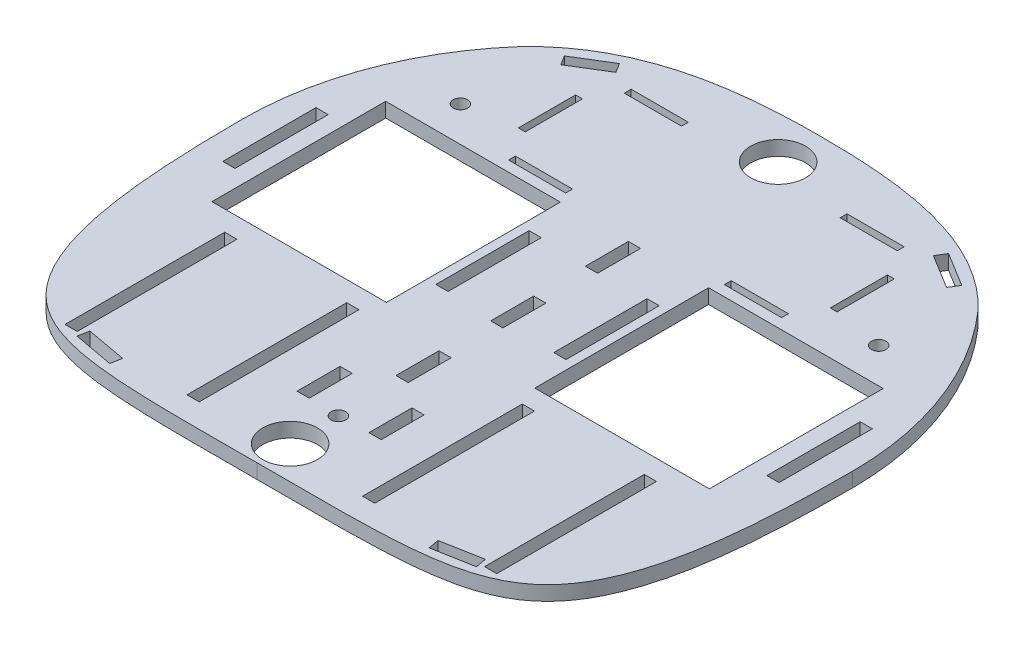
SolidWorks part; units mm, degrees
ref_plane "Front Plane" through (0, 0, 0) normal (0, 0, 1) x (1, 0, 0)
ref_plane "Top Plane" through (0, 0, 0) normal (0, 1, 0) x (1, 0, 0)
ref_plane "Right Plane" through (0, 0, 0) normal (1, 0, 0) x (0, 0, -1)
sketch "Sketch1" plane through (0, 0, 0) normal (0, 1, 0) x (1, 0, 0)
  line L0 (0, 0) -> (-157.9039, -157.9039) construction
  line L1 (0, -127) -> (0, 133.35) construction
  arc A0 (133.35, 0) -> (-133.35, 0) centre (0, 0) ccw
  spline S0 degree 3 poles (-133.35, 0) (-133.35, -51.198) (-123.8034, -129.8051) (-58.428, -127) (0, -127) knots 0 0 0 0 0.502616 1 1 1 1
  spline S1 degree 3 poles (133.35, 0) (133.35, -51.198) (123.8034, -129.8051) (58.428, -127) (0, -127) knots 0 0 0 0 0.502616 1 1 1 1
  dimension "D1" = 266.7
extrude "Base" add sketch "Sketch1" along normal blind 6.35
sketch "ShaftLayout" plane through (0, 6.35, 0) normal (0, 1, 0) x (1, 0, 0)
  line L0 (-133.35, 0) -> (133.35, 0) construction
  line L1 (0, 133.35) -> (0, -127) construction
  line L2 (-114.7053, -6.35) -> (-104.7993, -6.35)
  line L3 (-36.3853, -38) -> (-94.3853, -38)
  line L4 (-36.3853, -38) -> (-36.3853, 38)
  line L5 (-36.3853, 38) -> (-94.3853, 38)
  line L6 (-94.3853, -38) -> (-94.3853, 38)
  line L7 (-36.3853, -38) -> (-94.3853, 38) construction
  line L8 (-36.3853, 38) -> (-94.3853, -38) construction
  line L9 (-102.0053, -15.875) -> (-104.7993, -15.875)
  line L10 (-102.0053, -15.875) -> (-102.0053, 15.875)
  line L11 (-102.0053, 15.875) -> (-104.7993, 15.875)
  line L12 (-104.7993, -15.875) -> (-104.7993, 15.875)
  line L13 (-102.0053, -15.875) -> (-104.7993, 15.875) construction
  line L14 (-102.0053, 15.875) -> (-104.7993, -15.875) construction
  line L15 (-114.7053, -6.35) -> (-114.7053, 6.35)
  line L16 (-104.7993, -6.35) -> (-104.7993, 6.35)
  line L17 (-114.7053, 6.35) -> (-104.7993, 6.35)
  line L18 (-114.7053, -6.35) -> (-104.7993, 6.35) construction
  line L19 (-104.7993, -6.35) -> (-114.7053, 6.35) construction
  line L20 (-116.2928, -9.525) -> (-114.7053, -9.525)
  line L21 (-116.2928, -9.525) -> (-116.2928, 9.525)
  line L22 (-114.7053, -9.525) -> (-114.7053, 9.525)
  line L23 (-116.2928, 9.525) -> (-114.7053, 9.525)
  line L24 (-116.2928, -9.525) -> (-114.7053, 9.525) construction
  line L25 (-114.7053, -9.525) -> (-116.2928, 9.525) construction
  line L26 (-127.4053, -7.9375) -> (-116.2928, -7.9375)
  line L27 (-127.4053, -7.9375) -> (-127.4053, 7.9375)
  line L28 (-116.2928, -7.9375) -> (-116.2928, 7.9375)
  line L29 (-127.4053, 7.9375) -> (-116.2928, 7.9375)
  line L30 (-127.4053, -7.9375) -> (-116.2928, 7.9375) construction
  line L31 (-116.2928, -7.9375) -> (-127.4053, 7.9375) construction
  line L32 (-17.3353, -7.9375) -> (-28.4478, -7.9375)
  line L33 (-30.0353, -9.525) -> (-28.4478, -9.525)
  line L34 (-30.0353, -9.525) -> (-30.0353, 9.525)
  line L35 (-30.0353, 9.525) -> (-28.4478, 9.525)
  line L36 (-28.4478, -9.525) -> (-28.4478, 9.525)
  line L37 (-30.0353, -9.525) -> (-28.4478, 9.525) construction
  line L38 (-30.0353, 9.525) -> (-28.4478, -9.525) construction
  line L39 (-17.3353, -7.9375) -> (-17.3353, 7.9375)
  line L40 (-28.4478, -7.9375) -> (-28.4478, 7.9375)
  line L41 (-17.3353, 7.9375) -> (-28.4478, 7.9375)
  line L42 (-17.3353, -7.9375) -> (-28.4478, 7.9375) construction
  line L43 (-28.4478, -7.9375) -> (-17.3353, 7.9375) construction
  line L45 (-67.3853, -10.033) -> (-56.3853, -10.033)
  line L46 (-67.3853, -10.033) -> (-67.3853, 10.033)
  line L47 (-67.3853, 10.033) -> (-56.3853, 10.033)
  line L48 (-56.3853, -10.033) -> (-56.3853, 10.033)
  line L49 (-67.3853, -10.033) -> (-56.3853, 10.033) construction
  line L50 (-67.3853, 10.033) -> (-56.3853, -10.033) construction
  arc A0 (133.35, 0) -> (-133.35, 0) centre (0, 0) ccw construction
  point P10 (-65.3853, 0)
  point P15 (-103.4023, 0)
  point P20 (-29.2416, 0)
  point P21 (-109.7523, 0)
  point P22 (-115.4991, 0)
  point P23 (-121.8491, 0)
  point P40 (-61.8853, 0)
  point P41 (-22.8916, 0)
  dimension "D1" = 58
  dimension "D2" = 76
  dimension "D3" = 7.62
  dimension "D4" = 2.794
  dimension "D5" = 31.75
  dimension "D6" = 9.906
  dimension "D7" = 12.7
  dimension "D8" = 19.05
  dimension "D9" = 1.5875
  dimension "D10" = 12.7
  dimension "D11" = 15.875
  dimension "D12" = 19.05
  dimension "D13" = 1.5875
  dimension "D14" = 15.875
  dimension "D15" = 12.7
  dimension "D16" = 6.35
  dimension "D17" = 20.066
  dimension "D18" = 20
  dimension "D19" = 11
sketch "MotorLayout" plane through (0, 6.35, 0) normal (0, 1, 0) x (1, 0, 0)
  line L0 (-94.3853, -81.74) -> (-114.3853, -81.74) construction
  line L1 (-94.3853, -110.24) -> (-18.3853, -110.24)
  line L2 (-94.3853, -110.24) -> (-94.3853, -53.24)
  line L3 (-94.3853, -53.24) -> (-18.3853, -53.24)
  line L4 (-18.3853, -110.24) -> (-18.3853, -53.24)
  line L5 (-94.3853, -110.24) -> (-18.3853, -53.24) construction
  line L6 (-94.3853, -53.24) -> (-18.3853, -110.24) construction
  line L7 (-114.7053, -92.0587) -> (-104.7993, -92.0587)
  line L8 (-104.7993, -97.615) -> (-102.0053, -97.615)
  line L9 (-104.7993, -97.615) -> (-104.7993, -65.865)
  line L10 (-104.7993, -65.865) -> (-102.0053, -65.865)
  line L11 (-102.0053, -97.615) -> (-102.0053, -65.865)
  line L12 (-104.7993, -97.615) -> (-102.0053, -65.865) construction
  line L13 (-104.7993, -65.865) -> (-102.0053, -97.615) construction
  line L14 (-36.3853, -38) -> (-94.3853, -38) construction
  line L15 (-114.7053, -92.0587) -> (-114.7053, -71.4212)
  line L16 (-104.7993, -92.0587) -> (-104.7993, -71.4212)
  line L17 (-114.7053, -71.4212) -> (-104.7993, -71.4212)
  line L18 (-114.7053, -92.0587) -> (-104.7993, -71.4212) construction
  line L19 (-104.7993, -92.0587) -> (-114.7053, -71.4212) construction
  line L20 (-103.4023, -1000) -> (-103.4023, 49000) construction
  line L21 (-34.8953, -53.24) -> (-34.8953, -110.24) construction
  point P0 (-56.3853, -81.74)
  point P7 (-103.4023, -81.74)
  point P14 (-109.7523, -81.74)
  dimension "D1" = 20
  dimension "D2" = 76
  dimension "D3" = 57
  dimension "D4" = 2.794
  dimension "D5" = 15.24
  dimension "D6" = 31.75
  dimension "D7" = 20.6375
  dimension "D8" = 12.7
  dimension "D9" = 7.62
  dimension "D10" = 16.51
sketch "Sketch6" plane through (0, 6.35, 0) normal (0, 1, 0) x (1, 0, 0)
  line L0 (-36.3853, -38) -> (-36.3853, 38) construction
  line L1 (-32.4166, -38) -> (-108.7681, -38)
  line L2 (-32.4166, -38) -> (-32.4166, 38)
  line L3 (-32.4166, 38) -> (-108.7681, 38)
  line L4 (-108.7681, -38) -> (-108.7681, 38)
  line L5 (-28.4478, -9.525) -> (-28.4478, 9.525) construction
  line L6 (-104.7993, -15.875) -> (-104.7993, 15.875) construction
  line L7 (0, 133.35) -> (0, -127) construction
  line L8 (28.4478, 20.3835) -> (23.1138, -20.3835) construction
  line L9 (28.4478, -20.3835) -> (23.1138, 20.3835) construction
  line L10 (116.2928, 20.3835) -> (121.6268, -20.3835) construction
  line L11 (116.2928, -20.3835) -> (121.6268, 20.3835) construction
  line L12 (-133.35, 0) -> (133.35, 0) construction
  line L13 (-116.2928, -20.3835) -> (-121.6268, -20.3835)
  line L14 (-116.2928, -20.3835) -> (-116.2928, 20.3835)
  line L15 (-116.2928, 20.3835) -> (-121.6268, 20.3835)
  line L16 (-121.6268, -20.3835) -> (-121.6268, 20.3835)
  line L17 (-116.2928, -20.3835) -> (-121.6268, 20.3835) construction
  line L18 (-116.2928, 20.3835) -> (-121.6268, -20.3835) construction
  line L19 (-116.2928, -9.525) -> (-116.2928, 9.525) construction
  line L20 (-127.4053, 7.9375) -> (-116.2928, 7.9375) construction
  line L21 (-17.3353, 7.9375) -> (-28.4478, 7.9375) construction
  line L22 (-28.4478, -20.3835) -> (-23.1138, -20.3835)
  line L23 (-28.4478, -20.3835) -> (-28.4478, 20.3835)
  line L24 (-28.4478, 20.3835) -> (-23.1138, 20.3835)
  line L25 (-23.1138, -20.3835) -> (-23.1138, 20.3835)
  line L26 (-28.4478, -20.3835) -> (-23.1138, 20.3835) construction
  line L27 (-28.4478, 20.3835) -> (-23.1138, -20.3835) construction
  line L28 (23.1138, -20.3835) -> (23.1138, 20.3835)
  line L29 (28.4478, 20.3835) -> (23.1138, 20.3835)
  line L30 (28.4478, -20.3835) -> (28.4478, 20.3835)
  line L31 (28.4478, -20.3835) -> (23.1138, -20.3835)
  line L32 (121.6268, -20.3835) -> (121.6268, 20.3835)
  line L33 (116.2928, 20.3835) -> (121.6268, 20.3835)
  line L34 (116.2928, -20.3835) -> (116.2928, 20.3835)
  line L35 (116.2928, -20.3835) -> (121.6268, -20.3835)
  line L36 (108.7681, -38) -> (108.7681, 38)
  line L37 (32.4166, 38) -> (108.7681, 38)
  line L38 (32.4166, -38) -> (32.4166, 38)
  line L39 (32.4166, -38) -> (108.7681, -38)
  point P16 (-118.9598, 0)
  point P27 (-25.7808, 0)
  point P44 (25.7808, 0)
  point P45 (118.9598, 0)
  dimension "D1" = 3.9688
  dimension "D2" = 3.9688
  dimension "D3" = 12.446
  dimension "D4" = 12.446
  dimension "D5" = 5.334
  dimension "D6" = 5.334
extrude "WheelShaftCut" cut sketch "Sketch6" against normal through all
sketch "Sketch8" plane through (0, 6.35, 0) normal (0, 1, 0) x (1, 0, 0)
  line L0 (-94.3853, -81.74) -> (-18.3853, -81.74) construction
  line L1 (-18.3853, -110.24) -> (-18.3853, -53.24) construction
  line L2 (-94.3853, -53.24) -> (-18.3853, -53.24) construction
  line L3 (-35.7113, -116.59) -> (-41.0453, -116.59)
  line L4 (-35.7113, -116.59) -> (-35.7113, -46.763)
  line L5 (-35.7113, -46.763) -> (-41.0453, -46.763)
  line L6 (-41.0453, -116.59) -> (-41.0453, -46.763)
  line L7 (-35.7113, -116.59) -> (-41.0453, -46.763) construction
  line L8 (-35.7113, -46.763) -> (-41.0453, -116.59) construction
  line L9 (18.3853, -72.342) -> (13.0513, -91.138) construction
  line L10 (18.3853, -91.138) -> (13.0513, -72.342) construction
  line L11 (18.3853, -81.74) -> (15.7183, -81.74) construction
  line L12 (89.0513, -46.763) -> (94.3853, -116.59) construction
  line L13 (89.0513, -116.59) -> (94.3853, -46.763) construction
  line L14 (35.7113, -46.763) -> (41.0453, -116.59) construction
  line L15 (-89.0513, -116.59) -> (-94.3853, -116.59)
  line L16 (-89.0513, -116.59) -> (-89.0513, -46.763)
  line L17 (-89.0513, -46.763) -> (-94.3853, -46.763)
  line L18 (-94.3853, -116.59) -> (-94.3853, -46.763)
  line L19 (-89.0513, -116.59) -> (-94.3853, -46.763) construction
  line L20 (-89.0513, -46.763) -> (-94.3853, -116.59) construction
  line L21 (-94.3853, -110.24) -> (-94.3853, -53.24) construction
  line L22 (0, 133.35) -> (0, -127) construction
  line L23 (35.7113, -116.59) -> (41.0453, -46.763) construction
  line L24 (94.3853, -81.74) -> (18.3853, -81.74) construction
  line L25 (13.0513, -91.138) -> (13.0513, -72.342)
  line L26 (18.3853, -72.342) -> (13.0513, -72.342)
  line L27 (18.3853, -91.138) -> (18.3853, -72.342)
  line L28 (18.3853, -91.138) -> (13.0513, -91.138)
  line L29 (94.3853, -116.59) -> (94.3853, -46.763)
  line L30 (89.0513, -46.763) -> (94.3853, -46.763)
  line L31 (89.0513, -116.59) -> (89.0513, -46.763)
  line L32 (89.0513, -116.59) -> (94.3853, -116.59)
  line L33 (41.0453, -116.59) -> (41.0453, -46.763)
  line L34 (35.7113, -46.763) -> (41.0453, -46.763)
  line L35 (35.7113, -116.59) -> (35.7113, -46.763)
  line L36 (35.7113, -116.59) -> (41.0453, -116.59)
  line L42 (-18.3853, -81.74) -> (-15.7183, -81.74) construction
  line L44 (-18.3853, -91.138) -> (-13.0513, -91.138)
  line L45 (-18.3853, -91.138) -> (-18.3853, -72.342)
  line L46 (-18.3853, -72.342) -> (-13.0513, -72.342)
  line L47 (-13.0513, -91.138) -> (-13.0513, -72.342)
  line L48 (-18.3853, -91.138) -> (-13.0513, -72.342) construction
  line L49 (-18.3853, -72.342) -> (-13.0513, -91.138) construction
  point P6 (-63.7079, -81.74)
  point P7 (-38.2513, -81.74)
  point P19 (-91.5913, -81.74)
  point P39 (91.5913, -81.74)
  point P40 (38.2513, -81.74)
  dimension "D1" = 5.334
  dimension "D2" = 6.477
  dimension "D4" = 5.334
  dimension "D5" = 18.796
  dimension "D3" = 2
extrude "MotorCut" cut sketch "Sketch8" against normal through all
sketch "BatteryLayout" plane through (0, 6.35, 0) normal (0, 1, 0) x (1, 0, 0)
  line L0 (0, 133.35) -> (0, -127) construction
  line L1 (-32.4166, 38) -> (-108.7681, 38) construction
  line L2 (-66.675, 45.62) -> (66.675, 45.62)
  line L3 (-66.675, 45.62) -> (-66.675, 93.245)
  line L4 (-66.675, 93.245) -> (66.675, 93.245)
  line L5 (66.675, 45.62) -> (66.675, 93.245)
  line L6 (-66.675, 45.62) -> (66.675, 93.245) construction
  line L7 (-66.675, 93.245) -> (66.675, 45.62) construction
  arc A0 (133.35, 0) -> (-133.35, 0) centre (0, 0) ccw construction
  point P6 (0, 69.4325)
  dimension "D1" = 133.35
  dimension "D2" = 47.625
  dimension "D3" = 7.62
sketch "Sketch10" plane through (0, 6.35, 0) normal (0, 1, 0) x (1, 0, 0)
  line L0 (-66.675, 93.245) -> (66.675, 93.245) construction
  line L1 (-59.69, 42.62) -> (-34.69, 42.62)
  line L2 (-59.69, 42.62) -> (-59.69, 45.62)
  line L3 (-59.69, 45.62) -> (-34.69, 45.62)
  line L4 (-34.69, 42.62) -> (-34.69, 45.62)
  line L5 (-59.69, 42.62) -> (-34.69, 45.62) construction
  line L6 (-59.69, 45.62) -> (-34.69, 42.62) construction
  line L7 (-59.69, 96.245) -> (-34.69, 96.245)
  line L8 (-59.69, 96.245) -> (-59.69, 93.245)
  line L9 (-59.69, 93.245) -> (-34.69, 93.245)
  line L10 (-34.69, 96.245) -> (-34.69, 93.245)
  line L11 (-59.69, 96.245) -> (-34.69, 93.245) construction
  line L12 (-59.69, 93.245) -> (-34.69, 96.245) construction
  line L13 (-66.675, 45.62) -> (66.675, 45.62) construction
  line L14 (-66.675, 45.62) -> (-66.675, 93.245) construction
  line L15 (0, 69.4325) -> (-66.675, 69.4325) construction
  line L16 (-66.675, 56.9325) -> (-69.675, 56.9325)
  line L17 (-66.675, 56.9325) -> (-66.675, 81.9325)
  line L18 (-66.675, 81.9325) -> (-69.675, 81.9325)
  line L19 (-69.675, 56.9325) -> (-69.675, 81.9325)
  line L20 (0, 133.35) -> (0, -127) construction
  line L21 (59.69, 93.245) -> (34.69, 96.245) construction
  line L22 (59.69, 96.245) -> (34.69, 93.245) construction
  line L23 (59.69, 45.62) -> (34.69, 42.62) construction
  line L24 (59.69, 42.62) -> (34.69, 45.62) construction
  line L25 (69.675, 56.9325) -> (69.675, 81.9325)
  line L26 (66.675, 81.9325) -> (69.675, 81.9325)
  line L27 (66.675, 56.9325) -> (66.675, 81.9325)
  line L28 (66.675, 56.9325) -> (69.675, 56.9325)
  line L29 (34.69, 96.245) -> (34.69, 93.245)
  line L30 (59.69, 93.245) -> (34.69, 93.245)
  line L31 (59.69, 96.245) -> (59.69, 93.245)
  line L32 (59.69, 96.245) -> (34.69, 96.245)
  line L33 (34.69, 42.62) -> (34.69, 45.62)
  line L34 (59.69, 45.62) -> (34.69, 45.62)
  line L35 (59.69, 42.62) -> (59.69, 45.62)
  line L36 (59.69, 42.62) -> (34.69, 42.62)
  point P0 (-47.19, 44.12)
  point P5 (-47.19, 94.745)
  point P20 (-66.675, 69.4325)
  point P40 (66.675, 69.4325)
  point P41 (47.19, 94.745)
  point P42 (47.19, 44.12)
  dimension "D1" = 3
  dimension "D2" = 3
  dimension "D3" = 25
  dimension "D4" = 25
  dimension "D5" = 6.985
  dimension "D6" = 6.985
  dimension "D7" = 3
  dimension "D8" = 25
extrude "VelcroCut" cut sketch "Sketch10" against normal through all
sketch "Sketch11" plane through (0, 6.35, 0) normal (0, 1, 0) x (1, 0, 0)
  line L0 (0, 133.35) -> (0, -127) construction
  line L1 (-133.35, 0) -> (133.35, 0) construction
  circle A1 centre (0, -91.44) radius 3.175
  circle A2 centre (-91.44, 53.34) radius 3.175
  circle A3 centre (91.44, 53.34) radius 3.175
  dimension "D1" = 6.35
  dimension "D2" = 53.34
  dimension "D3" = 6.35
  dimension "D6" = 91.44
  dimension "D4" = 91.44
extrude "ScrewCut" cut sketch "Sketch11" against normal through all
sketch "Sketch13" plane through (0, 6.35, 0) normal (0, 1, 0) x (1, 0, 0)
  line L0 (0, 133.35) -> (0, -127) construction
  line L1 (-2.667, 19.204) -> (2.667, 19.204)
  line L2 (-2.667, 19.204) -> (-2.667, 38)
  line L3 (-2.667, 38) -> (2.667, 38)
  line L4 (2.667, 19.204) -> (2.667, 38)
  line L5 (-2.667, 19.204) -> (2.667, 38) construction
  line L6 (-2.667, 38) -> (2.667, 19.204) construction
  line L7 (108.7681, 38) -> (32.4166, 38) construction
  line L8 (-2.667, -22.198) -> (2.667, -22.198)
  line L9 (-2.667, -22.198) -> (-2.667, -3.402)
  line L10 (-2.667, -3.402) -> (2.667, -3.402)
  line L11 (2.667, -22.198) -> (2.667, -3.402)
  line L12 (-2.667, -22.198) -> (2.667, -3.402) construction
  line L13 (-2.667, -3.402) -> (2.667, -22.198) construction
  line L14 (-2.667, -63.6) -> (2.667, -63.6)
  line L15 (-2.667, -63.6) -> (-2.667, -44.804)
  line L16 (-2.667, -44.804) -> (2.667, -44.804)
  line L17 (2.667, -63.6) -> (2.667, -44.804)
  line L18 (-2.667, -63.6) -> (2.667, -44.804) construction
  line L19 (-2.667, -44.804) -> (2.667, -63.6) construction
  point P0 (0, 28.602)
  point P9 (0, 0)
  point P10 (0, -12.8)
  point P15 (0, -54.202)
  dimension "D1" = 5.334
  dimension "D2" = 18.796
  dimension "D3" = 0
  dimension "D5" = 101.6
  dimension "D4" = 3
extrude "SupportStrutCut" cut sketch "Sketch13" against normal through all
sketch "Sketch16" plane through (0, 6.35, 0) normal (0, 1, 0) x (1, 0, 0)
  line L0 (0, -1000) -> (0, 49000) construction
  line L1 (-100.0331, 133.35) -> (-100.0331, 88.1793)
  line L2 (-100.0331, 133.35) -> (100.0331, 133.35)
  line L3 (100.0331, 133.35) -> (100.0331, 88.1793)
  arc A0 (133.35, 0) -> (-133.35, 0) centre (0, 0) ccw construction
  spline S0 degree 3 poles (-100.0331, 88.1793) (-73.9195, 115.9102) (-34.9729, 119.8228) (0, 119.8228) knots 0 0 0 0 1 1 1 1
  spline S1 degree 3 poles (100.0331, 88.1793) (73.9195, 115.9102) (34.9729, 119.8228) (0, 119.8228) knots 0 0 0 0 1 1 1 1
extrude "EmptySpaceTrim" cut sketch "Sketch16" against normal through all
sketch "Sketch15" plane through (0, 6.35, 0) normal (0, 1, 0) x (1, 0, 0)
  line L0 (-78.1477, -1116.59) -> (-78.1477, 48883.41) construction
  line L2 (-87.3468, -118.3963) -> (-69.8208, -121.6168)
  line L3 (-87.3468, -118.3963) -> (-86.4746, -113.6498)
  line L4 (-69.8208, -121.6168) -> (-68.9486, -116.8703)
  line L5 (-86.4746, -113.6498) -> (-68.9486, -116.8703)
  line L6 (-87.3468, -118.3963) -> (-68.9486, -116.8703) construction
  line L7 (-69.8208, -121.6168) -> (-86.4746, -113.6498) construction
  line L8 (-84.3532, 90.1176) -> (-69.4173, 99.287)
  line L9 (-84.3532, 90.1176) -> (-86.8782, 94.2303)
  line L10 (-69.4173, 99.287) -> (-71.9422, 103.3998)
  line L11 (-86.8782, 94.2303) -> (-71.9422, 103.3998)
  line L12 (-84.3532, 90.1176) -> (-71.9422, 103.3998) construction
  line L13 (-69.4173, 99.287) -> (-86.8782, 94.2303) construction
  line L14 (0, -1000) -> (0, 49000) construction
  line L15 (69.4173, 99.287) -> (86.8782, 94.2303) construction
  line L16 (84.3532, 90.1176) -> (71.9422, 103.3998) construction
  line L17 (69.8208, -121.6168) -> (86.4746, -113.6498) construction
  line L18 (87.3468, -118.3963) -> (68.9486, -116.8703) construction
  line L19 (88.7973, -116.59) -> (66.5019, -116.59) construction
  line L20 (86.8782, 94.2303) -> (71.9422, 103.3998)
  line L21 (69.4173, 99.287) -> (71.9422, 103.3998)
  line L22 (84.3532, 90.1176) -> (86.8782, 94.2303)
  line L23 (84.3532, 90.1176) -> (69.4173, 99.287)
  line L24 (86.4746, -113.6498) -> (68.9486, -116.8703)
  line L25 (69.8208, -121.6168) -> (68.9486, -116.8703)
  line L26 (87.3468, -118.3963) -> (86.4746, -113.6498)
  line L27 (87.3468, -118.3963) -> (69.8208, -121.6168)
  point P4 (-78.1477, 96.7587)
  point P7 (-78.1477, -117.6333)
  point P30 (78.1477, -117.6333)
  point P31 (78.1477, 96.7587)
  dimension "D1" = 4.826
  dimension "D2" = 17.526
  dimension "D3" = 17.526
  dimension "D4" = 4.826
extrude "TapeSensorCut" cut sketch "Sketch15" against normal through all
sketch "Sketch17" plane through (0, 6.35, 0) normal (0, 1, 0) x (1, 0, 0)
  line L0 (0, -1000) -> (0, 49000) construction
  line L1 (-34.69, 93.245) -> (34.69, 93.245) construction
  circle A0 centre (0, 100.8346) radius 12
  circle A1 centre (0, 100.8346) radius 5 construction
  circle A2 centre (0, -112.5625) radius 12
  dimension "D1" = 24
  dimension "D2" = 10
  dimension "D3" = 24
extrude "CasterCut" cut sketch "Sketch17" against normal through all
sketch "Layer1Limits" plane through (0, 0, 0) normal (0, 1, 0) x (1, 0, 0)
  line L0 (-127, 119.8228) -> (127, -134.1772) construction
  line L1 (-127, -134.1772) -> (127, -134.1772) construction
  line L2 (-127, -134.1772) -> (-127, 119.8228) construction
  line L3 (-127, 119.8228) -> (127, 119.8228) construction
  line L4 (127, -134.1772) -> (127, 119.8228) construction
  line L5 (127, 119.8228) -> (-127, -134.1772) construction
  line L6 (0, -1000) -> (0, 49000) construction
  point P4 (0, -7.1772)
  dimension "D1" = 254
  dimension "D2" = 254
